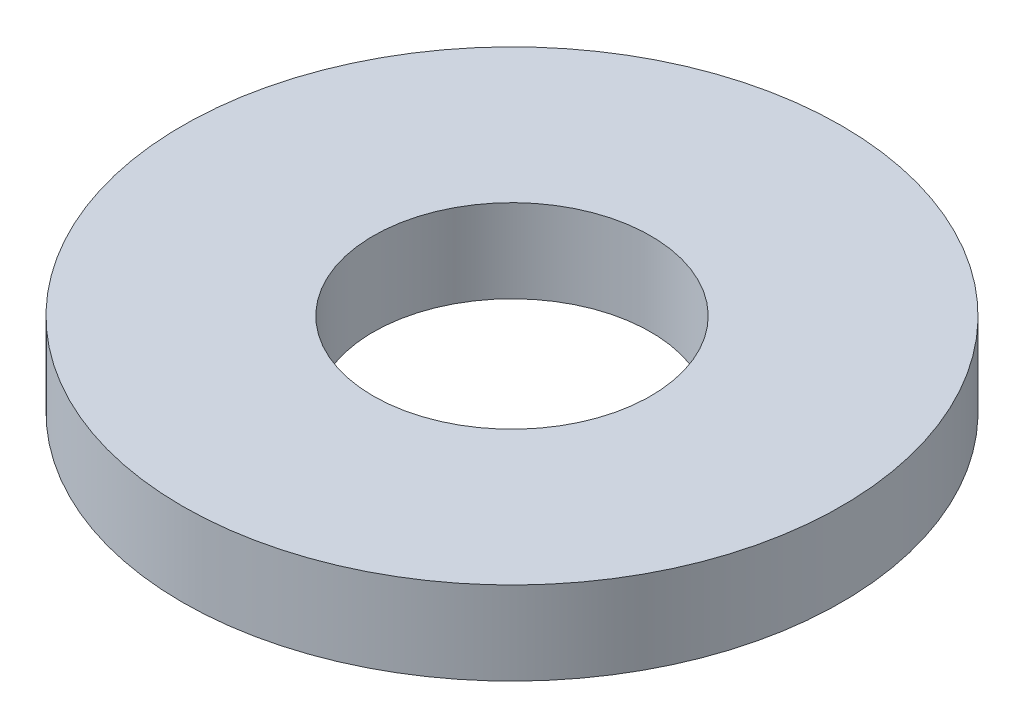
SolidWorks part; units mm, degrees
ref_plane "Front Plane" through (0, 0, 0) normal (0, 0, 1) x (1, 0, 0)
ref_plane "Top Plane" through (0, 0, 0) normal (0, 1, 0) x (1, 0, 0)
ref_plane "Right Plane" through (0, 0, 0) normal (1, 0, 0) x (0, 0, -1)
sketch "Sketch1" plane through (0, 0, 0) normal (0, 1, 0) x (1, 0, 0)
  circle A0 centre (0, 0) radius 95
  dimension "FLANGE_OD" = 190
extrude "Boss-Extrude1" add sketch "Sketch1" along normal blind 24
sketch "Sketch2" plane through (0, 0, 0) normal (0, 1, 0) x (1, 0, 0)
  circle A0 centre (0, 0) radius 40
  dimension "BORE_D" = 80
extrude "Cut-Extrude1" cut sketch "Sketch2" along normal through all
sketch "Sketch3" plane through (0, 24, 0) normal (0, 1, 0) x (1, 0, 0)
  circle A0 centre (0, 0) radius 30.1369 construction
  circle A1 centre (-30.1369, 0) radius 2.4857
  dimension "BOLT_D" = 4.9713
  dimension "BOLT_PCD" = 60.2737
extrude "Cut-Extrude2" cut sketch "Sketch3" against normal blind 22.1289 rebuild error yes
pattern_circular "CirPattern1" count 8 over 360 rebuild error yes
